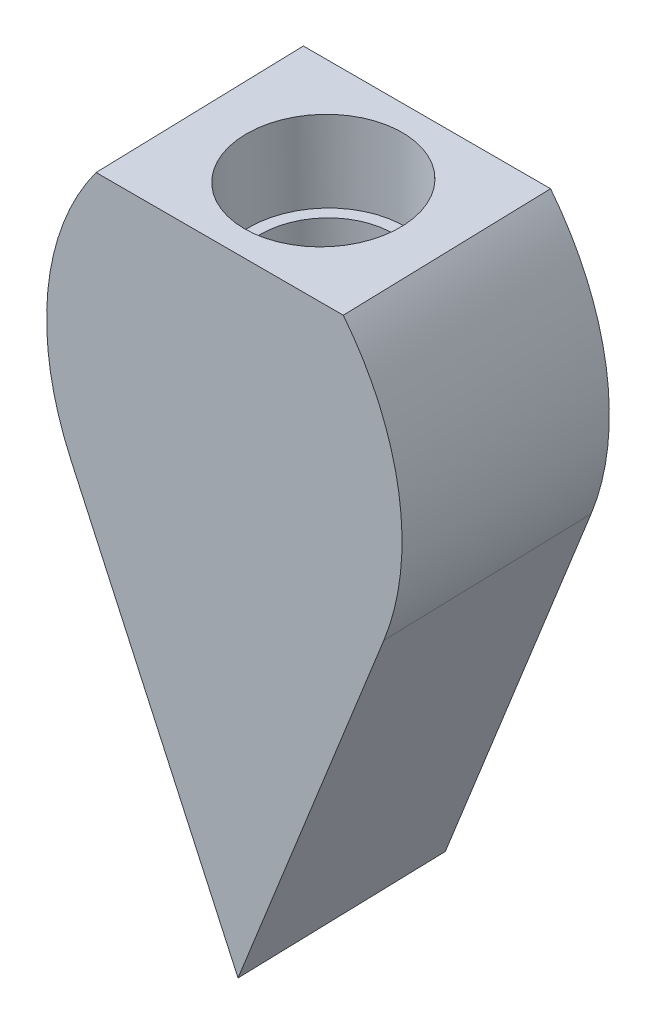
SolidWorks part; units mm, degrees
note: The reader was unsure of these and kept them because the rebuilt part matched: shared geometry of "Sketch4<5>".
ref_plane "Front Plane" through (0, 0, 0) normal (0, 0, 1) x (1, 0, 0)
ref_plane "Top Plane" through (0, 0, 0) normal (0, 1, 0) x (1, 0, 0)
ref_plane "Right Plane" through (0, 0, 0) normal (1, 0, 0) x (0, 0, -1)
sketch "Sketch2" plane through (0, 0.0215, -0.5805) normal (0, -0.0284, 0.9996) x (1, 0, 0)
  line L1 (0.4147, -7.8159) -> (0.4147, -23.1159) construction
  line L4 (-10.3604, -5.4088) -> (-2.9935, -23.1159)
  line L11 (4.9147, -7.8159) -> (9.4301, -3.3005)
  line L19 (4.9147, -7.8159) -> (-4.0853, -7.8159)
  line L20 (-4.0853, -7.8159) -> (-8.6008, -3.3005)
  line L21 (11.1898, -5.4088) -> (3.8228, -23.1159)
  line L24 (-8.6008, -3.3005) -> (-13.1162, 1.2149)
  line L26 (-10.3604, -5.4088) -> (-13.1162, 1.2149)
  line L27 (9.4301, -3.3005) -> (13.9455, 1.2149)
  line L28 (11.1898, -5.4088) -> (13.9455, 1.2149)
  line L31 (-2.9935, -23.1159) -> (3.8228, -23.1159)
  point P8 (0.4147, -23.1159)
  point P13 (0, -26.5147)
  dimension "D2" = 15.3
extrude "Boss-Extrude1" add sketch "Sketch2" along normal up to surface (4.35 mm away) and the other way up to surface (3.2 mm away)
sketch "Sketch4" plane through (0, -7.8078, -0.2221) normal (0, 0.9996, 0.0284) x (1, 0, 0)
  line L0 (-4.0853, 3.7809) -> (4.9147, -3.7691) construction
  line L1 (4.9147, 3.7809) -> (-4.0853, -3.7691) construction
  circle A0 centre (0.4147, 0.0059) radius 2.875
  circle A1 centre (0.4147, 0.0059) radius 2.45
  dimension "D1" = 5.75
  dimension "D2" = 4.9
extrude "Cut-Extrude2" cut sketch "Sketch4" against normal blind 10 contours A1
extrude "Cut-Extrude3" cut sketch "Sketch4<5>" against normal blind 3
sketch "Sketch4<5>" plane through (0, -7.8078, -0.2221) normal (0, 0.9996, 0.0284) x (1, 0, 0) same geometry as "Sketch4"
sketch "Sketch5" plane through (0, -0.1072, 3.7676) normal (0, -0.0284, 0.9996) x (1, 0, 0)
  line L4 (4.9147, -7.8109) -> (13.9455, 1.2199) construction
  line L5 (13.9455, 1.2199) -> (3.8228, -23.1109) construction
  line L6 (-4.0853, -7.8109) -> (-8.1512, -3.7451)
  line L8 (-4.0853, -7.8109) -> (-13.1162, 1.2199) construction
  line L9 (-13.1162, 1.2199) -> (-2.9935, -23.1109) construction
  line L10 (-8.1512, -3.7451) -> (-10.1987, -5.7926)
  line L11 (-10.1987, -5.7926) -> (-13.1162, 1.2199)
  line L12 (8.9805, -3.7451) -> (13.9455, 1.2199)
  line L13 (13.9455, 1.2199) -> (11.2056, -5.3658)
  line L24 (-13.1162, 1.2199) -> (-8.1512, -3.7451)
  line L27 (8.9805, -3.7451) -> (11.2056, -5.3658)
  line M10 (3.8228, -23.1109) -> (13.9455, 1.2199)
  line M11 (13.9455, 1.2199) -> (4.9147, -7.8109)
  line M13 (-4.0853, -7.8109) -> (-13.1162, 1.2199)
  line M14 (-13.1162, 1.2199) -> (-2.9935, -23.1109)
  dimension "D3" = 5.75
fillet "Fillet1" radius 10 2 edges at (13.9455, 1.2196, 0.0288) (-13.1162, 1.2196, 0.0288)
extrude "Cut-Extrude4" [suppressed] cut sketch "Sketch5" against normal up to next contours L27 M11 M10 | L10 M13 M14
sketch "Sketch6" plane through (0, -0.1072, 3.7676) normal (0, -0.0284, 0.9996) x (1, 0, 0)
  line L0 (-2.9935, -23.1109) -> (0.4147, -31.3027)
  line L1 (0.4147, -31.3027) -> (3.8228, -23.1109)
  line L2 (-5.2837, -17.6061) -> (-2.9935, -23.1109) construction
  line L3 (6.1131, -17.6061) -> (3.8228, -23.1109) construction
  line L4 (3.8228, -23.1109) -> (-2.9935, -23.1109)
extrude "Boss-Extrude2" add sketch "Sketch6" against normal up to surface (7.55 mm away) contours L0 L1 L4 up to face at (0.4147, -16.0093, -4.2378)
